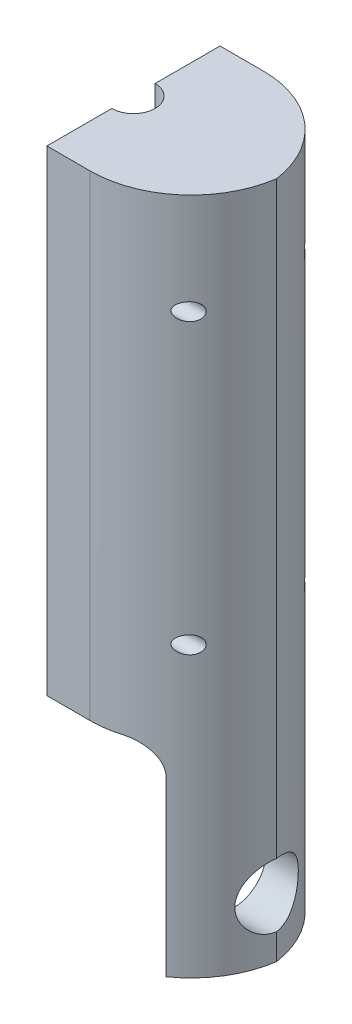
SolidWorks part; units mm, degrees
ref_plane "Plan de face" through (0, 0, 0) normal (0, 0, 1) x (1, 0, 0)
ref_plane "Plan de dessus" through (0, 0, 0) normal (0, 1, 0) x (1, 0, 0)
ref_plane "Plan de droite" through (0, 0, 0) normal (1, 0, 0) x (0, 0, -1)
sketch "Esquisse1" plane through (0, 0, 0) normal (0, 0, 1) x (1, 0, 0)
  line L0 (-50, 160) -> (-50, -70)
  line L1 (-50, -70) -> (-35, -70)
  line L2 (-35, -70) -> (-35, 0)
  line L3 (-35, 0) -> (35, 0)
  line L4 (35, 0) -> (35, -70)
  line L5 (35, -70) -> (50, -70)
  line L6 (50, -70) -> (50, 160)
  line L7 (50, 160) -> (-50, 160)
  line L8 (0, 0) -> (50, 0) construction
  line L9 (0, 0) -> (0, 160) construction
  point P14 (0, 0)
  dimension "D1" = 230
  dimension "D2" = 100
  dimension "D3" = 70
  dimension "D4" = 70
extrude "Boss.-Extru.1" add sketch "Esquisse1" along normal blind 60
fillet "Congé4" radius 35 1 edges at (-50, 45, 60)
fillet "Congé5" radius 35 1 edges at (-50, 45, 0)
fillet "Congé6" radius 35 2 edges at (50, 45, 0) (50, 45, 60)
fillet "Congé12" radius 10 2 edges at (-35, 0, 29.5186) (35, 0, 30)
sketch "Esquisse3" plane through (35, 0, 0) normal (-1, 0, 0) x (0, 0, 1)
  line L0 (30, -70) -> (30, -50) construction
  line L1 (53.7228, -70) -> (6.2772, -70) construction
  circle A1 centre (30, -50) radius 11
  dimension "D1" = 22
  dimension "D2" = 20
extrude "Enlèv. mat.-Extru.4" cut sketch "Esquisse3" against normal blind 50
sketch "Esquisse5" plane through (0, 160, 0) normal (0, 1, 0) x (1, 0, 0)
  line L0 (0, -60) -> (0, 0)
  line L1 (15, -60) -> (-15, -60) construction
  arc A0 (0, -60) -> (0, 0) centre (-29.0756, -30) cw
extrude "Enlèv. mat.-Extru.8" cut sketch "Esquisse5" against normal blind 251
sketch "Esquisse6" plane through (0, 0, 0) normal (-1, 0, 0) x (0, 0, 1)
  line L0 (30, 160) -> (30, 0) construction
  line L1 (60, 160) -> (0, 160) construction
  line L2 (60, 0) -> (0, 0) construction
  line L4 (60, 0) -> (60, 160) construction
  line L5 (60, 80) -> (0, 80) construction
  line L6 (0, 0) -> (0, 160) construction
  circle A0 centre (10, 130) radius 2
  circle A1 centre (50, 130) radius 2
  circle A2 centre (50, 30) radius 2
  circle A3 centre (10, 30) radius 2
  dimension "D1" = 40
  dimension "D2" = 50
  dimension "D3" = 4
extrude "Enlèv. mat.-Extru.9" cut sketch "Esquisse6" against normal blind 58
sketch "Esquisse9" plane through (0, 160, 0) normal (0, 1, 0) x (1, 0, 0)
  line L0 (0, -60) -> (0, 0) construction
  line L1 (49.641, -30) -> (0, -30) construction
  arc A0 (0, -22.5) -> (0, -37.5) centre (0, -30) cw
  point P8 (7.5, -30)
  dimension "D1" = 15
extrude "Enlèv. mat.-Extru.12" cut sketch "Esquisse9" against normal blind 179 and the other way through all flip side to cut
shell "Coque1" thickness 5 removed face at (14.0465, 160, 30)
ref_plane "Plan2" through (49.641, 0, 0) normal (-1, 0, 0) x (0, 0, 1)
sketch "Esquisse11" plane through (49.641, 0, 0) normal (-1, 0, 0) x (0, 0, 1)
  circle A0 centre (50, 30) radius 2 construction
  circle A1 centre (50, 130) radius 2 construction
  circle A2 centre (50, 30) radius 2 construction
  circle A3 centre (50, 130) radius 2 construction
  circle A4 centre (10, 130) radius 2 construction
  circle A5 centre (10, 30) radius 2 construction
  circle A6 centre (10, 130) radius 2 construction
  circle A7 centre (10, 30) radius 2 construction
  circle A8 centre (50, 130) radius 3
  circle A9 centre (10, 130) radius 3
  circle A10 centre (50, 30) radius 3
  circle A11 centre (10, 30) radius 3
  dimension "D1" = 1
  dimension "D2" = 1
  dimension "D3" = 1
  dimension "D4" = 1
extrude "Enlèv. mat.-Extru.14" cut sketch "Esquisse11" along normal blind 20
sketch "Esquisse12" plane through (0, 160, 0) normal (0, 1, 0) x (1, 0, 0)
  line L0 (15, 0) -> (0, 0) construction
  line L1 (0, -22.5) -> (0, 0) construction
  line L2 (0, -60) -> (0, -37.5) construction
  line L3 (15, -60) -> (0, -60) construction
  line L4 (15, 0) -> (0, 0)
  line L5 (0, -22.5) -> (0, 0)
  line L6 (0, -60) -> (0, -37.5)
  line L7 (15, -60) -> (0, -60)
  arc A0 (0, -37.5) -> (0, -22.5) centre (0, -30) ccw construction
  arc A1 (15, -60) -> (49.641, -30) centre (15, -25) ccw construction
  arc A2 (49.641, -30) -> (15, 0) centre (15, -35) ccw construction
  arc A3 (0, -37.5) -> (0, -22.5) centre (0, -30) ccw
  arc A4 (15, -60) -> (49.641, -30) centre (15, -25) ccw
  arc A5 (49.641, -30) -> (15, 0) centre (15, -35) ccw
extrude "Boss.-Extru.2" add sketch "Esquisse12" along normal blind 5
